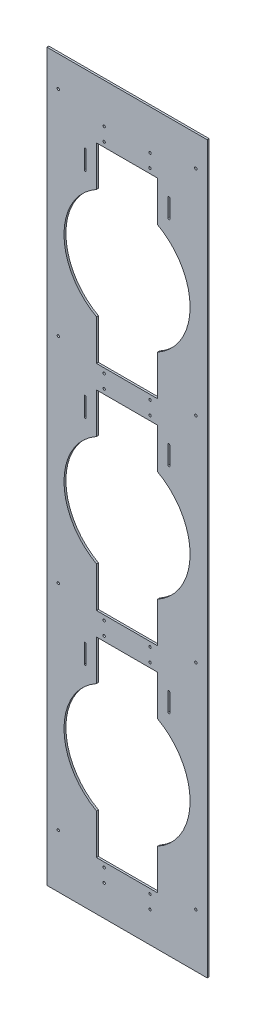
SolidWorks part; units mm, degrees
material "PC High Viscosity"
ref_plane "Front Plane" through (0, 0, 0) normal (0, 0, 1) x (1, 0, 0)
ref_plane "Top Plane" through (0, 0, 0) normal (0, 1, 0) x (1, 0, 0)
ref_plane "Right Plane" through (0, 0, 0) normal (1, 0, 0) x (0, 0, -1)
sketch "Sketch1" plane through (0, 0, 0) normal (0, 0, 1) x (1, 0, 0)
  line L0 (-101.6, 797.56) -> (101.6, 797.56)
  line L1 (-266.7, 0) -> (266.7, 0)
  line L2 (-266.7, 0) -> (-266.7, 2413)
  line L3 (-266.7, 2413) -> (266.7, 2413)
  line L4 (266.7, 0) -> (266.7, 2413)
  line L5 (-101.6, 162.56) -> (101.6, 162.56)
  line L6 (-209.55, 480.06) -> (209.55, 480.06) construction
  line L7 (-101.6, 162.56) -> (-101.6, 296.788)
  line L8 (101.6, 162.56) -> (101.6, 296.788)
  line L9 (101.6, 797.56) -> (101.6, 663.332)
  line L10 (-101.6, 797.56) -> (-101.6, 663.332)
  line L11 (-101.6, 1508.76) -> (-101.6, 1374.532)
  line L12 (-101.6, 873.76) -> (-101.6, 1007.988)
  line L13 (-101.6, 873.76) -> (101.6, 873.76)
  line L14 (101.6, 873.76) -> (101.6, 1007.988)
  line L15 (101.6, 1508.76) -> (101.6, 1374.532)
  line L16 (-101.6, 1508.76) -> (101.6, 1508.76)
  line L17 (-101.6, 2219.96) -> (-101.6, 2085.732)
  line L18 (-101.6, 1584.96) -> (-101.6, 1719.188)
  line L19 (-101.6, 1584.96) -> (101.6, 1584.96)
  line L20 (101.6, 1584.96) -> (101.6, 1719.188)
  line L21 (101.6, 2219.96) -> (101.6, 2085.732)
  line L22 (-101.6, 2219.96) -> (101.6, 2219.96)
  arc A0 (-101.6, 663.332) -> (-101.6, 296.788) centre (0, 480.06) ccw
  arc A1 (101.6, 296.788) -> (101.6, 663.332) centre (0, 480.06) ccw
  arc A2 (-101.6, 1374.532) -> (-101.6, 1007.988) centre (0, 1191.26) ccw
  arc A3 (101.6, 1007.988) -> (101.6, 1374.532) centre (0, 1191.26) ccw
  arc A4 (-101.6, 2085.732) -> (-101.6, 1719.188) centre (0, 1902.46) ccw
  arc A5 (101.6, 1719.188) -> (101.6, 2085.732) centre (0, 1902.46) ccw
  circle A6 centre (0, 480.06) radius 241.3 construction
  point P11 (0, 797.56)
  point P12 (0, 162.56)
  dimension "D3" = 419.1
  dimension "D9" = 482.6
  dimension "D10" = 25.4
  dimension "D1" = 2413
  dimension "D2" = 533.4
  dimension "D4" = 635
  dimension "D5" = 480.06
  dimension "D6" = 203.2
  dimension "D8" = 711.2
  dimension "D11" = 57.15
  dimension "D7" = 3
extrude "Boss-Extrude1" add sketch "Sketch1" along normal blind 6.35
hole_wizard "5/16 (0.3125) Diameter Hole1" positions "Sketch2" profile "Sketch3" hole size "5/16" standard "ANSI Inch" end condition through all
sketch "Sketch2" plane through (0, 0, 6.35) normal (0, 0, 1) x (1, 0, 0)
  line L0 (0, 0) -> (0, 2413) construction
  line L1 (-266.7, 0) -> (266.7, 0) construction
  line L2 (266.7, 2413) -> (-266.7, 2413) construction
  line L4 (-76.2, 146.685) -> (-76.2, 102.235) construction
  line L5 (-76.2, 124.46) -> (0, 124.46) construction
  line L7 (-101.6, 162.56) -> (101.6, 162.56) construction
  line L8 (-266.7, 2413) -> (-266.7, 0) construction
  point P0 (-76.2, 146.685)
  point P4 (-76.2, 102.235)
  point P8 (-228.6, 177.8)
  point P31 (76.2, 102.235)
  point P32 (76.2, 146.685)
  point P43 (-76.2, 857.885)
  point P44 (-76.2, 813.435)
  point P45 (76.2, 813.435)
  point P46 (76.2, 857.885)
  point P47 (-76.2, 1569.085)
  point P48 (-76.2, 1524.635)
  point P49 (76.2, 1524.635)
  point P50 (76.2, 1569.085)
  point P51 (-76.2, 2280.285)
  point P52 (-76.2, 2235.835)
  point P53 (76.2, 2235.835)
  point P54 (76.2, 2280.285)
  point P57 (228.6, 177.8)
  point P62 (-228.6, 889)
  point P63 (228.6, 889)
  point P64 (-228.6, 1600.2)
  point P65 (228.6, 1600.2)
  point P66 (-228.6, 2311.4)
  point P67 (228.6, 2311.4)
  dimension "D1" = 44.45
  dimension "D2" = 38.1
  dimension "D3" = 76.2
  dimension "D5" = 711.2
  dimension "D6" = 177.8
  dimension "D7" = 38.1
  dimension "D4" = 4
sketch "Sketch3" plane through (-76.2, 146.685, 6.35) normal (1, 0, 0) x (0, -1, 0)
  line L0 (0, 0) -> (0, 6.35)
  line L1 (0, 6.35) -> (3.9687, 6.35)
  line L2 (3.9687, 6.35) -> (3.9687, 0)
  line L5 (3.9687, 0) -> (0, 0)
  line L11 (0, -6.35) -> (0, 107.95) construction
  dimension "Thru Hole Dia." = 7.9375
  dimension "Thru Hole Depth" = 6.35
hole_wizard "1/4 (0.25) Diameter Slot1" positions "Sketch4" profile "Sketch5" size "1/4" standard "ANSI Inch" slot yes end condition through all
sketch "Sketch4" plane through (0, 0, 6.35) normal (0, 0, 1) x (1, 0, 0)
  line L0 (-139.0015, 763.3445) -> (-139.0015, 696.6695) construction
  line L1 (0, 797.56) -> (0, 162.56) construction
  line L2 (101.6, 797.56) -> (-101.6, 797.56) construction
  line L3 (-101.6, 162.56) -> (101.6, 162.56) construction
  line L5 (-101.6, 797.56) -> (-101.6, 663.332) construction
  line L6 (139.0015, 763.3445) -> (139.0015, 696.6695) construction
  line L7 (-139.0015, 1474.5445) -> (-139.0015, 1407.8695) construction
  line L8 (139.0015, 1474.5445) -> (139.0015, 1407.8695) construction
  line L9 (-139.0015, 2185.7445) -> (-139.0015, 2119.0695) construction
  line L10 (139.0015, 2185.7445) -> (139.0015, 2119.0695) construction
  line L11 (139.0015, 730.007) -> (139.0015, 1441.207) construction
  point P0 (-139.0015, 730.007)
  point P20 (139.0015, 730.007)
  point P30 (-139.0015, 1441.207)
  point P35 (139.0015, 1441.207)
  point P36 (-139.0015, 2152.407)
  point P41 (139.0015, 2152.407)
  dimension "D5" = 711.2
  dimension "D1" = 66.675
  dimension "D2" = 37.4015
  dimension "D3" = 66.675
  dimension "D4" = 3
sketch "Sketch5" plane through (-139.0015, 730.007, 6.35) normal (1, 0, 0) x (0, -1, 0)
  line L0 (0, 0) -> (0, 6.35)
  line L1 (0, 6.35) -> (3.175, 6.35)
  line L2 (3.175, 6.35) -> (3.175, 0)
  line L5 (3.175, 0) -> (0, 0)
  line L11 (0, -6.35) -> (0, 107.95) construction
  dimension "Thru Hole Dia." = 6.35
  dimension "Thru Hole Depth" = 6.35
equation "\"D1@Sketch2\"=1.5+.25"
equation "\"D2@Sketch4\"=1.3875+.17/2"
